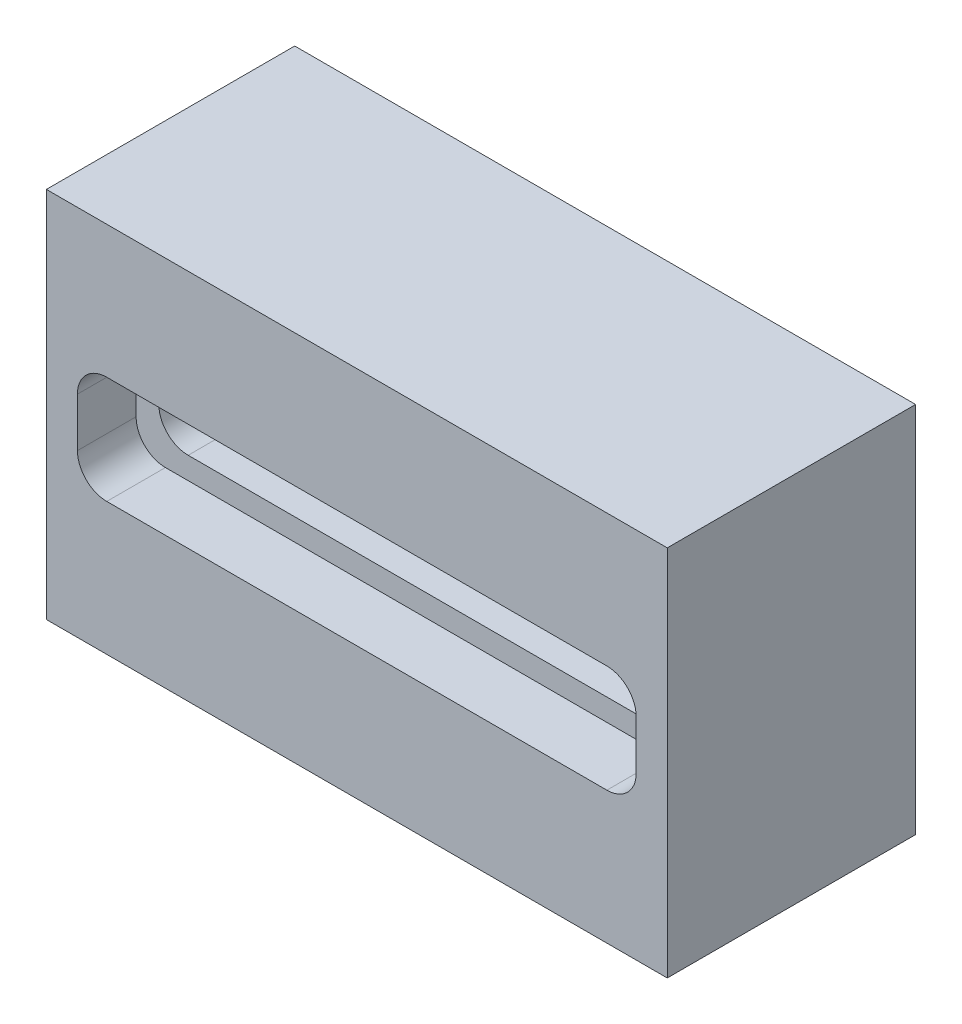
SolidWorks part; units mm, degrees
ref_plane "Front Plane" through (0, 0, 0) normal (0, 0, 1) x (1, 0, 0)
ref_plane "Top Plane" through (0, 0, 0) normal (0, 1, 0) x (1, 0, 0)
ref_plane "Right Plane" through (0, 0, 0) normal (1, 0, 0) x (0, 0, -1)
sketch "Sketch1" plane through (0, 0, 0) normal (0, 1, 0) x (1, 0, 0)
  line L1 (0, 0) -> (127, 0)
  line L2 (0, 0) -> (0, 50.8)
  line L3 (0, 50.8) -> (127, 50.8)
  line L4 (127, 0) -> (127, 50.8)
  dimension "D1" = 50.8
  dimension "D2" = 127
extrude "Boss-Extrude1" add sketch "Sketch1" along normal blind 76.2
sketch "Sketch2" plane through (0, 0, 0) normal (0, 0, 1) x (1, 0, 0)
  line L1 (0, 0) -> (63.5, 0)
  line L2 (0, 0) -> (0, 38.1)
  line L3 (0, 38.1) -> (63.5, 38.1)
  line L4 (63.5, 0) -> (63.5, 38.1)
  line L5 (17, 44.6) -> (110, 44.6)
  line L6 (11, 38.6) -> (11, 37.6)
  line L7 (17, 31.6) -> (110, 31.6)
  line L8 (116, 38.6) -> (116, 37.6)
  line L9 (11, 44.6) -> (116, 31.6) construction
  line L10 (11, 31.6) -> (116, 44.6) construction
  arc A0 (110, 44.6) -> (116, 38.6) centre (110, 38.6) cw
  arc A1 (110, 31.6) -> (116, 37.6) centre (110, 37.6) ccw
  arc A2 (11, 37.6) -> (17, 31.6) centre (17, 37.6) ccw
  arc A3 (17, 44.6) -> (11, 38.6) centre (17, 38.6) ccw
  dimension "D5" = 6
  dimension "D1" = 38.1
  dimension "D2" = 63.5
  dimension "D3" = 105
  dimension "D4" = 13
sketch "Sketch3" plane through (0, 0, 0) normal (0, 0, 1) x (1, 0, 0)
  line L1 (0, 0) -> (63.5, 0)
  line L2 (0, 0) -> (0, 38.1)
  line L3 (0, 38.1) -> (63.5, 38.1)
  line L4 (63.5, 0) -> (63.5, 38.1)
  line L5 (12.35, 49.1) -> (114.65, 49.1)
  line L6 (6.35, 43.1) -> (6.35, 33.1)
  line L7 (12.35, 27.1) -> (114.65, 27.1)
  line L8 (120.65, 43.1) -> (120.65, 33.1)
  line L9 (6.35, 49.1) -> (120.65, 27.1) construction
  line L10 (6.35, 27.1) -> (120.65, 49.1) construction
  arc A0 (12.35, 49.1) -> (6.35, 43.1) centre (12.35, 43.1) ccw
  arc A1 (6.35, 33.1) -> (12.35, 27.1) centre (12.35, 33.1) ccw
  arc A2 (114.65, 27.1) -> (120.65, 33.1) centre (114.65, 33.1) ccw
  arc A3 (114.65, 49.1) -> (120.65, 43.1) centre (114.65, 43.1) cw
  dimension "D4" = 6
  dimension "D1" = 63.5
  dimension "D2" = 38.1
  dimension "D3" = 114.3
  dimension "D5" = 10
extrude "Cut-Extrude2" cut sketch "Sketch3" against normal blind 12 contours L5 A3 L8 A2 L7 A1 L6 A0
extrude "Cut-Extrude3" cut sketch "Sketch2" against normal through all contours L5 A0 L8 A1 L7 A2 L6 A3
